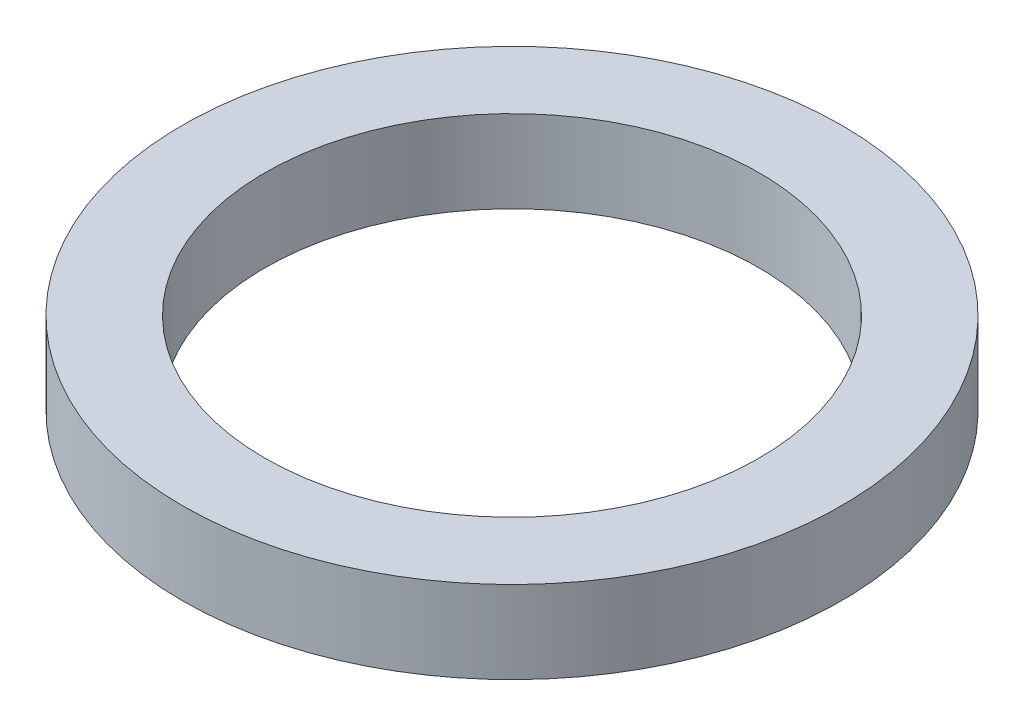
SolidWorks part; units mm, degrees
ref_plane "Front Plane" through (0, 0, 0) normal (0, 0, 1) x (1, 0, 0)
ref_plane "Top Plane" through (0, 0, 0) normal (0, 1, 0) x (1, 0, 0)
ref_plane "Right Plane" through (0, 0, 0) normal (1, 0, 0) x (0, 0, -1)
sketch "Sketch1" plane through (0, 0, 0) normal (0, 1, 0) x (1, 0, 0)
  circle A0 centre (0, 0) radius 4
  circle A1 centre (0, 0) radius 3
  dimension "D1" = 8
  dimension "D2" = 6
extrude "Boss-Extrude1" add sketch "Sketch1" along normal blind 1
equation "\"N_pin\"= 24"
equation "\"R_pin\"= 60"
equation "\"d_pin\"= 13"
equation "\"e\"= 1.5"
equation "\"t_disk\"= 5"
equation "\"N_outpin\"= 8"
equation "\"R_outpin\"= 34"
equation "\"d_outpin\"= 13"
equation "\"N_lobes\"= \"N_pin\" - 1"
equation "\"d_outhole\"= \"d_outpin\" + 2 * \"e\""
equation "\"ratio\"= \"N_lobes\""
equation "\"d_center\"= 24"
equation "\"a_hole1\"= 0 / \"N_lobes\""
equation "\"a_hole2\"= 360 / \"N_disk\" / \"N_lobes\""
equation "\"a_hole3\"= 720 / \"N_disk\" / \"N_lobes\""
equation "\"N_disk\"= 3"
equation "\"t_gap\"= 0.5"
equation "\"L_stack\"= \"N_disk\" * \"t_disk\" + (\"N_disk\" - 1) * \"t_gap\""
equation "\"d_pinshaft\"= 6"
equation "\"d_ecc\"= 15"
equation "\"d_outbrg\"= 47"
equation "\"w_outbrg\"= 7"
equation "\"d_outshaft\"= 35"
equation "\"w_brg\"= 5"
equation "\"c_run\"= 0.5"
equation "\"c_ax\"= 2 * \"t_gap\""
equation "\"D_pocket\"= 2 * \"R_pin\" + \"d_pin\" + 2 * \"c_run\""
equation "\"h_pocket\"= \"L_stack\" + 2 * \"c_ax\""
equation "\"t_floor\"= 8"
equation "\"d_insert\"= 5.6"
equation "\"N_bolt\"= 8"
equation "\"R_bolt\"= \"D_pocket\" / 2 + 2 + \"d_insert\" / 2"
equation "\"D_housing\"= 2 * (\"R_bolt\" + \"d_insert\" / 2 + 2.5)"
equation "\"D1@Sketch1\"=\"d_pinshaft\"+2"
equation "\"D2@Sketch1\"=\"d_pinshaft\""
equation "\"D1@Boss-Extrude1\"=\"t_gap\"*2"
